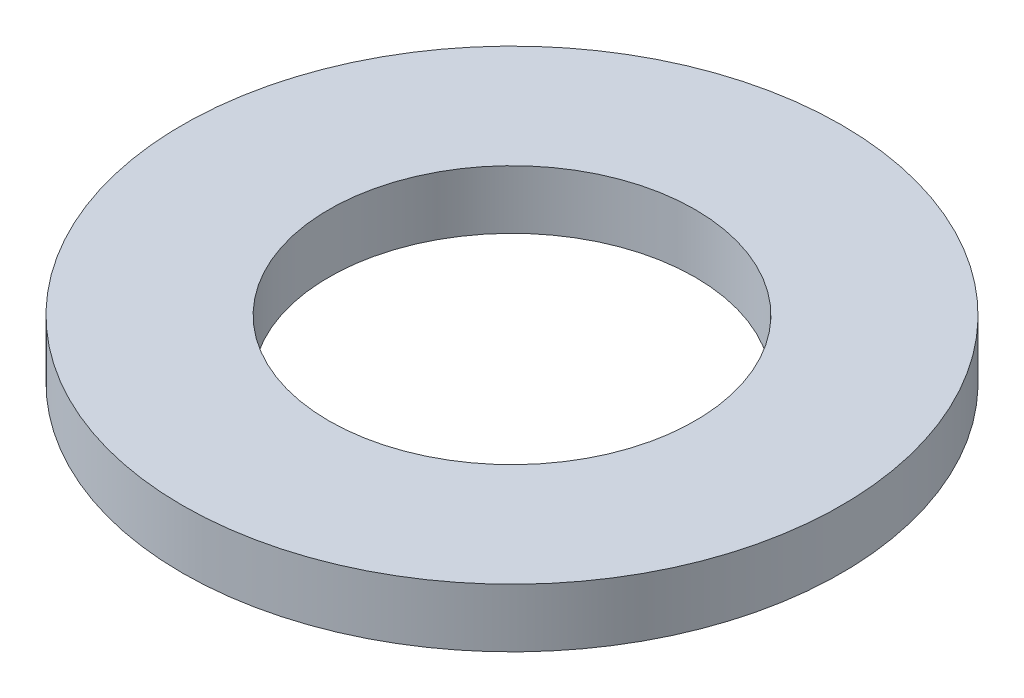
SolidWorks part; units mm, degrees
ref_plane "Front Plane" through (0, 0, 0) normal (0, 0, 1) x (1, 0, 0)
ref_plane "Top Plane" through (0, 0, 0) normal (0, 1, 0) x (1, 0, 0)
ref_plane "Right Plane" through (0, 0, 0) normal (1, 0, 0) x (0, 0, -1)
sketch "Sketch1" plane through (0, 0, 0) normal (0, 1, 0) x (1, 0, 0)
  circle A0 centre (0, 0) radius 67.5
  dimension "FLANGE_OD" = 135
extrude "Boss-Extrude1" add sketch "Sketch1" along normal blind 12
sketch "Sketch2" plane through (0, 0, 0) normal (0, 1, 0) x (1, 0, 0)
  circle A0 centre (0, 0) radius 37.5
  dimension "BORE_D" = 75
extrude "Cut-Extrude1" cut sketch "Sketch2" along normal through all
sketch "Sketch3" plane through (0, 12, 0) normal (0, 1, 0) x (1, 0, 0)
  circle A0 centre (0, 0) radius 27.792 construction
  circle A1 centre (-27.792, 0) radius 2.5049
  dimension "BOLT_D" = 5.0097
  dimension "BOLT_PCD" = 55.5841
extrude "Cut-Extrude2" cut sketch "Sketch3" against normal blind 8.1318 rebuild error yes
pattern_circular "CirPattern1" count 3 over 360 rebuild error yes
